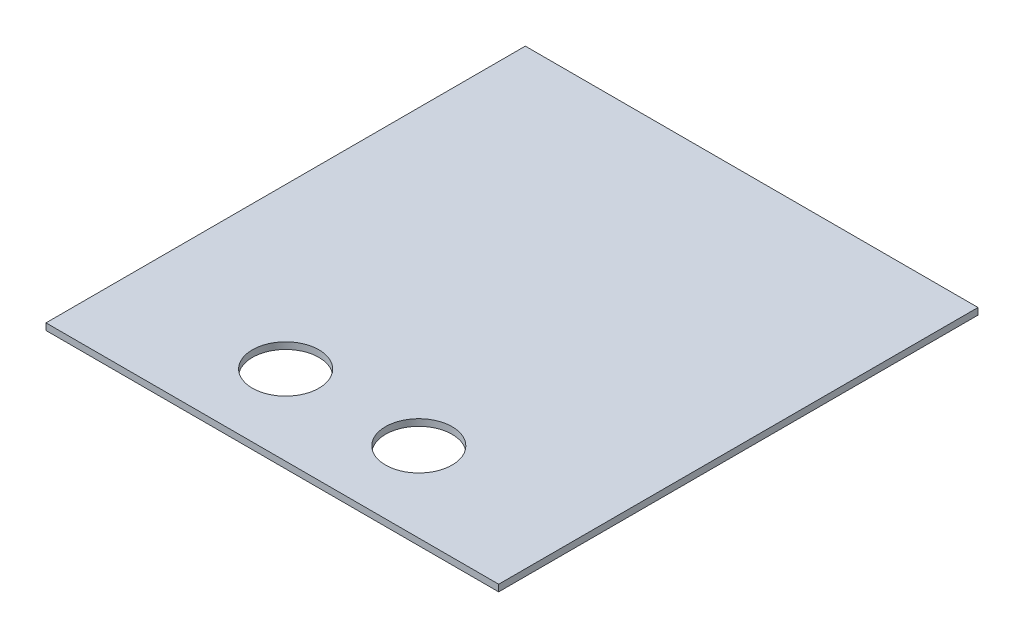
SolidWorks part; units mm, degrees
ref_plane "Front Plane" through (0, 0, 0) normal (0, 0, 1) x (1, 0, 0)
ref_plane "Top Plane" through (0, 0, 0) normal (0, 1, 0) x (1, 0, 0)
ref_plane "Right Plane" through (0, 0, 0) normal (1, 0, 0) x (0, 0, -1)
sketch "Sketch1" plane through (0, 0, 0) normal (0, 1, 0) x (1, 0, 0)
  line L1 (0, 0) -> (215.9, 0)
  line L2 (0, 0) -> (0, 228.6)
  line L3 (0, 228.6) -> (215.9, 228.6)
  line L4 (215.9, 0) -> (215.9, 228.6)
  dimension "D1" = 215.9
  dimension "D2" = 228.6
extrude "Boss-Extrude1" add sketch "Sketch1" along normal blind 3.175
sketch "Sketch2" plane through (0, 3.175, 0) normal (0, 1, 0) x (1, 0, 0)
  line L0 (139.7, 38.1) -> (76.2, 38.1) construction
  line L2 (139.7, 38.1) -> (215.9, 38.1) construction
  line L3 (215.9, 0) -> (215.9, 228.6) construction
  line L4 (76.2, 38.1) -> (0, 38.1) construction
  line L5 (0, 0) -> (215.9, 0) construction
  line L6 (0, 228.6) -> (0, 0) construction
  circle A0 centre (139.7, 38.1) radius 15.875
  circle A1 centre (76.2, 38.1) radius 15.875
  dimension "D1" = 31.75
  dimension "D2" = 38.1
  dimension "D3" = 63.5
extrude "Cut-Extrude1" cut sketch "Sketch2" against normal through all
